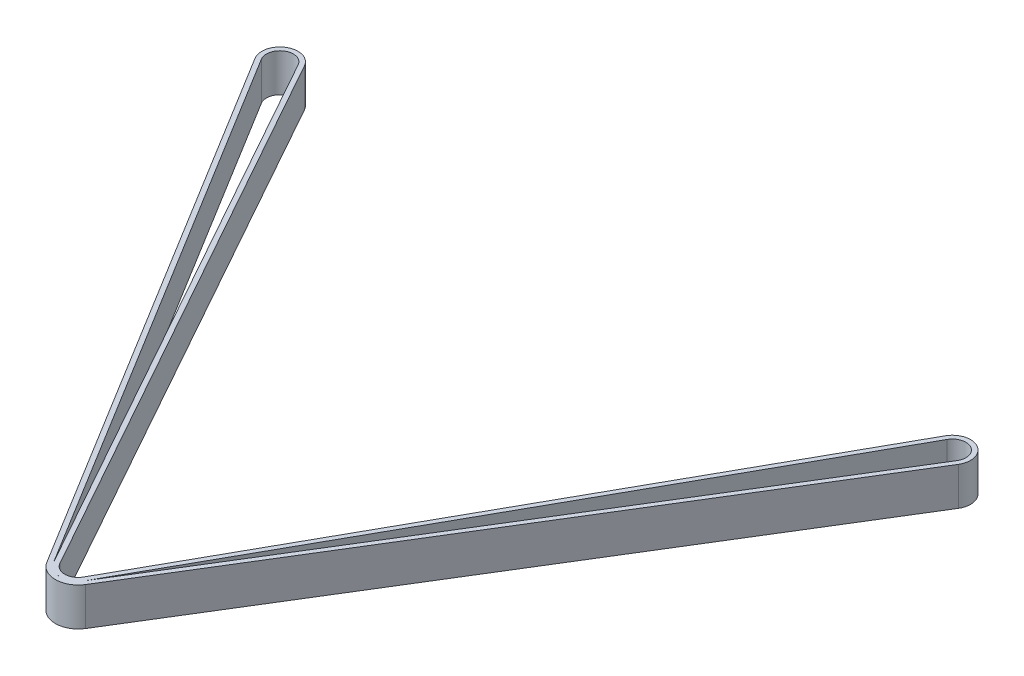
SolidWorks part; units mm, degrees
ref_plane "Front" through (0, 0, 0) normal (0, 0, 1) x (1, 0, 0)
ref_plane "Top" through (0, 0, 0) normal (0, 1, 0) x (1, 0, 0)
ref_plane "Right" through (0, 0, 0) normal (1, 0, 0) x (0, 0, -1)
ref_axis "X" through (-80.9, 0, 0) along (1, 0, 0)
ref_axis "Y" through (0, -50, 0) along (0, 1, 0)
ref_axis "Z" through (0, 0, -80.9) along (0, 0, 1)
sketch "Sketch1" plane through (0, 0, 0) normal (0, 1, 0) x (1, 0, 0)
  line L0 (-50, 0) -> (50, 0) construction
  line L1 (0, 0) -> (0, -80) construction
  line L2 (-47.9521, 1.1425) -> (-2.0479, -81.1425) construction
  line L3 (2.0479, -81.1425) -> (47.9521, 1.1425) construction
  line L4 (51.9976, -1.2282) -> (2.5862, -81.5902) construction
  line L5 (-2.5862, -81.5902) -> (-51.9976, -1.2282) construction
  line L6 (-2.8801, -81.7709) -> (-52.2915, -1.409)
  line L7 (-47.6508, 1.3105) -> (-1.7466, -80.9744)
  line L8 (1.7466, -80.9744) -> (47.6508, 1.3105)
  line L9 (52.2915, -1.409) -> (2.8801, -81.7709)
  line L10 (-2.2923, -81.4095) -> (-51.7037, -1.0475)
  line L11 (-48.2534, 0.9744) -> (-2.3492, -81.3105)
  line L12 (2.3492, -81.3105) -> (48.2534, 0.9744)
  line L13 (51.7037, -1.0475) -> (2.2923, -81.4095)
  line L14 (0, -82.69) -> (0, -82.691) construction
  circle A0 centre (-50, 0) radius 2 construction
  circle A1 centre (50, 0) radius 2 construction
  arc A2 (-47.9521, 1.1425) -> (-51.9976, -1.2282) centre (-50, 0) ccw construction
  arc A3 (51.9976, -1.2282) -> (47.9521, 1.1425) centre (50, 0) ccw construction
  circle A4 centre (0, -80) radius 2 construction
  arc A5 (-2.0479, -81.1425) -> (2.0479, -81.1425) centre (0, -80) ccw construction
  arc A6 (-2.5862, -81.5902) -> (2.5862, -81.5902) centre (0, -80) ccw construction
  arc A7 (-47.6508, 1.3105) -> (-52.2915, -1.409) centre (-50, 0) ccw
  arc A8 (-1.7466, -80.9744) -> (1.7466, -80.9744) centre (0, -80) ccw
  arc A9 (52.2915, -1.409) -> (47.6508, 1.3105) centre (50, 0) ccw
  arc A10 (-2.8801, -81.7709) -> (2.8801, -81.7709) centre (0, -80) ccw
  arc A11 (-48.2534, 0.9744) -> (-51.7037, -1.0475) centre (-50, 0) ccw
  arc A12 (-2.3492, -81.3105) -> (2.3492, -81.3105) centre (0, -80) ccw
  arc A13 (51.7037, -1.0475) -> (48.2534, 0.9744) centre (50, 0) ccw
  arc A14 (-2.2923, -81.4095) -> (2.2923, -81.4095) centre (0, -80) ccw
  dimension "D2" = 4
  dimension "D3" = 4
  dimension "D1" = 100
  dimension "D4" = 80
  dimension "D7" = 0.001
  dimension "D5" = 0.345
  dimension "D6" = 0.345
extrude "Boss-Extrude1" add sketch "Sketch1" along normal mid plane 5.67
